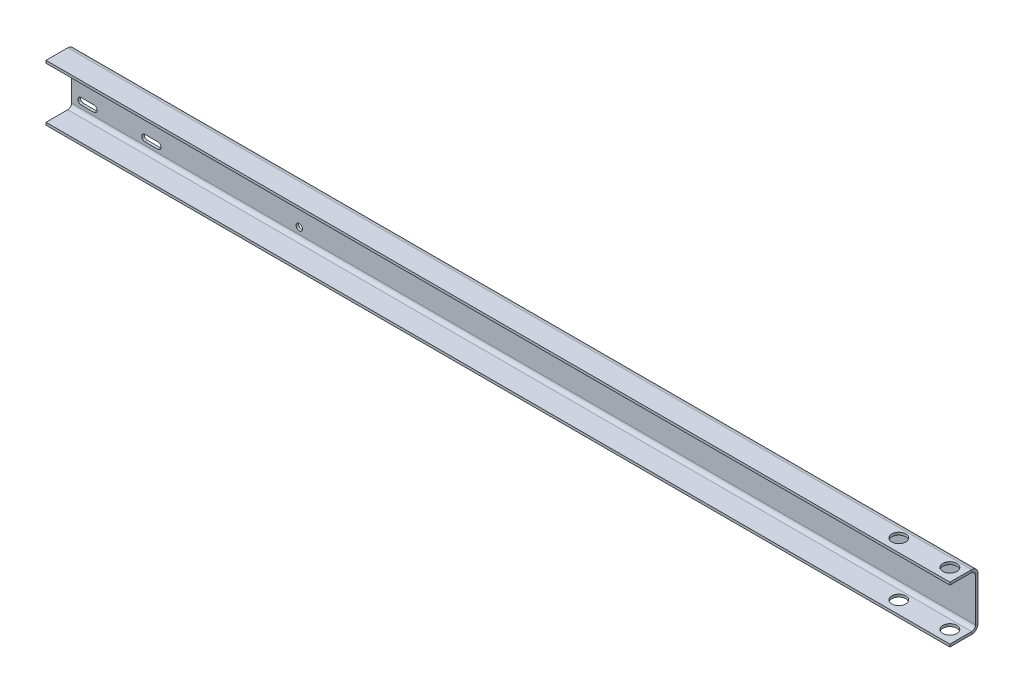
SolidWorks part; units mm, degrees
note: The reader was unsure of these and kept them because the rebuilt part matched: flange length of "Edge-Flange1", "Edge-Flange2".
material "ASTM A36 Steel"
ref_plane "Front Plane" through (0, 0, 0) normal (0, 0, 1) x (1, 0, 0)
ref_plane "Top Plane" through (0, 0, 0) normal (0, 1, 0) x (1, 0, 0)
ref_plane "Right Plane" through (0, 0, 0) normal (1, 0, 0) x (0, 0, -1)
sketch "Sketch1" plane through (0, 0, 0) normal (0, 0, 1) x (1, 0, 0)
  line L1 (549.481, 88) -> (-865.519, 88)
  line L2 (549.481, 88) -> (549.481, 0)
  line L3 (549.481, 0) -> (-865.519, 0)
  line L4 (-865.519, 88) -> (-865.519, 0)
  dimension "D1" = 88
  dimension "D2" = 1415
base flange "Base-Flange1" sketch "Sketch1" thickness 4 reverse thickness direction no parameters "D1"=2.5
edge flange "Edge-Flange1" sketch "Sketch8" flange angle 90 flange length 44 flange position material inside bend radius 6 thickness 4 relief rectangular parameters "D6"=10
sketch "Sketch8" plane through (0, 88, 0) normal (0, -1, 0) x (1, 0, 0)
  line L1 (549.481, 0) -> (-865.519, 0) construction
  line L2 (-865.519, 0) -> (-865.519, 40)
  line L3 (-865.519, 40) -> (549.481, 40)
  line L4 (549.481, 40) -> (549.481, 0)
  line L5 (549.481, 0) -> (-865.519, 0)
bend "EdgeBend1" bend radius 6 bend angle 90 parameters "D5"=1
edge flange "Edge-Flange2" sketch "Sketch11" flange angle 90 flange length 44 flange position material inside bend radius 6 thickness 4 relief rectangular parameters "D6"=10
sketch "Sketch11" plane through (0, 0, 0) normal (0, 1, 0) x (-1, 0, 0)
  line L1 (865.519, 0) -> (-549.481, 0) construction
  line L2 (-549.481, 0) -> (-549.481, 40)
  line L3 (-549.481, 40) -> (865.519, 40)
  line L4 (865.519, 40) -> (865.519, 0)
  line L5 (865.519, 0) -> (-549.481, 0)
bend "EdgeBend2" bend radius 6 bend angle 90 parameters "D5"=2
sketch "Sketch12" plane through (0, 0, 0) normal (0, -1, 0) x (1, 0, 0)
  line L0 (549.481, 40) -> (549.481, 6) construction
  circle A0 centre (529.481, 20) radius 11
  circle A1 centre (449.481, 20) radius 11
  dimension "D3" = 22
  dimension "D4" = 22
  dimension "D1" = 20
  dimension "D2" = 80
extrude "Cut-Extrude1" cut sketch "Sketch12" against normal through all both and the other way through all normal cut yes
sketch "Sketch13" plane through (0, 0, -4) normal (0, 0, -1) x (-1, 0, 0)
  line L0 (850.519, 20) -> (830.519, 20) construction
  line L1 (850.519, 15) -> (830.519, 15)
  line L2 (850.519, 25) -> (830.519, 25)
  line L3 (865.519, 0) -> (-549.481, 0) construction
  line L4 (750.519, 20) -> (730.519, 20) construction
  line L5 (750.519, 15) -> (730.519, 15)
  line L6 (750.519, 25) -> (730.519, 25)
  line L9 (865.519, 78) -> (865.519, 10) construction
  arc A0 (850.519, 15) -> (850.519, 25) centre (850.519, 20) ccw
  arc A1 (830.519, 25) -> (830.519, 15) centre (830.519, 20) ccw
  arc A4 (750.519, 15) -> (750.519, 25) centre (750.519, 20) ccw
  arc A5 (730.519, 25) -> (730.519, 15) centre (730.519, 20) ccw
  point P2 (835.519, 20)
  point P3 (840.519, 20)
  point P7 (740.519, 20)
  dimension "D5" = 20
  dimension "D6" = 100
  dimension "D7" = 15
  dimension "D8" = 0
  dimension "D1" = 20
  dimension "D2" = 10
  dimension "D3" = 20
  dimension "D4" = 10
extrude "Cut-Extrude2" cut sketch "Sketch13" against normal through all normal cut yes
sketch "Sketch16" plane through (0, 0, -4) normal (0, 0, -1) x (-1, 0, 0)
  line L0 (865.519, 20) -> (509.019, 20) construction
  line L1 (865.519, 78) -> (865.519, 10) construction
  circle A0 centre (509.019, 20) radius 5
extrude "Cut-Extrude4" cut sketch "Sketch16" against normal blind 10 normal cut yes
sketch "Bend-Lines1" [suppressed] plane through (0, 0, 0) normal (0, 1, 0) x (1, 0, 0)
sketch "Bounding-Box1" [suppressed] plane through (0, 0, 0) normal (0, 1, 0) x (1, 0, 0)
sheet metal parameters "Sheet-Metal1" thickness 4 parameters "D1"=2.5
flat pattern "Flat-Pattern1" [suppressed]
sketch "Bend-Lines2" plane through (0, 0, 0) normal (0, 1, 0) x (1, 0, 0)
sketch3d "Bounding-Box2" [suppressed]
  line L0 (865.519, 0, 0) -> (-299.481, 0, 0) construction
  line L1 (865.519, 88, 0) -> (-299.481, 88, 0) construction
  line L2 (865.519, 0, 0) -> (865.519, 88, 0) construction
  line L3 (-299.481, 0, 0) -> (-299.481, 88, 0) construction
sheet metal parameters "Sheet-Metal2" thickness 4 parameters "D1"=2.5
flat pattern "Flat-Pattern1"
sketch "Bend-Lines2" plane through (0, 0, 0) normal (0, 0, 1) x (1, 0, 0)
  line L0 (299.481, 84.2832) -> (-865.519, 84.2832) construction
  line L1 (299.481, 84.2832) -> (-865.519, 84.2832) construction
sketch3d "Bounding-Box2" [suppressed]
  line L0 (-865.519, 0, 0) -> (299.481, 0, 0) construction
  line L1 (-865.519, 124.5664, 0) -> (299.481, 124.5664, 0) construction
  line L2 (-865.519, 0, 0) -> (-865.519, 124.5664, 0) construction
  line L3 (299.481, 0, 0) -> (299.481, 124.5664, 0) construction
bend of the flat pattern "Flatten-<EdgeBend1>1"
sheet metal parameters "Sheet-Metal3" thickness 4 parameters "D1"=2.5
flat pattern "Flat-Pattern1"
sketch "Bend-Lines2" plane through (0, 0, 0) normal (0, 0, 1) x (1, 0, 0)
  line L0 (299.481, 84.2832) -> (-865.519, 84.2832) construction
  line L1 (299.481, 84.2832) -> (-865.519, 84.2832) construction
  line L2 (-865.519, 3.7168) -> (299.481, 3.7168) construction
  line L3 (-865.519, 3.7168) -> (299.481, 3.7168) construction
sketch3d "Bounding-Box2" [suppressed]
  line L0 (-865.519, -36.5664, 0) -> (299.481, -36.5664, 0) construction
  line L1 (-865.519, 124.5664, 0) -> (299.481, 124.5664, 0) construction
  line L2 (-865.519, -36.5664, 0) -> (-865.519, 124.5664, 0) construction
  line L3 (299.481, -36.5664, 0) -> (299.481, 124.5664, 0) construction
bend of the flat pattern "Flatten-<EdgeBend1>1"
bend of the flat pattern "Flatten-<EdgeBend2>1"
sheet metal parameters "Sheet-Metal4" thickness 4 parameters "D1"=2.5
flat pattern "Flat-Pattern1"
sketch "Bend-Lines2" plane through (0, 0, 0) normal (0, 0, 1) x (1, 0, 0)
  line L0 (299.481, 84.2832) -> (-865.519, 84.2832) construction
  line L1 (299.481, 84.2832) -> (-865.519, 84.2832) construction
  line L2 (-865.519, 3.7168) -> (299.481, 3.7168) construction
  line L3 (-865.519, 3.7168) -> (299.481, 3.7168) construction
sketch3d "Bounding-Box2" [suppressed]
  line L0 (-865.519, -36.5664, 0) -> (299.481, -36.5664, 0) construction
  line L1 (-865.519, 124.5664, 0) -> (299.481, 124.5664, 0) construction
  line L2 (-865.519, -36.5664, 0) -> (-865.519, 124.5664, 0) construction
  line L3 (299.481, -36.5664, 0) -> (299.481, 124.5664, 0) construction
bend of the flat pattern "Flatten-<EdgeBend1>1"
bend of the flat pattern "Flatten-<EdgeBend2>1"
sheet metal parameters "Sheet-Metal5" thickness 4 parameters "D1"=2.5
flat pattern "Flat-Pattern1" [suppressed]
sketch "Bend-Lines2" plane through (0, 0, 0) normal (0, 0, 1) x (1, 0, 0)
  line L0 (299.481, 84.2832) -> (-865.519, 84.2832) construction
  line L1 (299.481, 84.2832) -> (-865.519, 84.2832) construction
  line L2 (-865.519, 3.7168) -> (299.481, 3.7168) construction
  line L3 (-865.519, 3.7168) -> (299.481, 3.7168) construction
sketch3d "Bounding-Box2" [suppressed]
  line L0 (-865.519, -36.5664, 0) -> (299.481, -36.5664, 0) construction
  line L1 (-865.519, 124.5664, 0) -> (299.481, 124.5664, 0) construction
  line L2 (-865.519, -36.5664, 0) -> (-865.519, 124.5664, 0) construction
  line L3 (299.481, -36.5664, 0) -> (299.481, 124.5664, 0) construction
bend of the flat pattern "Flatten-<EdgeBend1>1"
bend of the flat pattern "Flatten-<EdgeBend2>1"
sketch "Sketch14-1" [suppressed] plane through (0, 3.4336, -4) normal (0, 0, -1) x (1, 0, 0)
  line L0 (-865.519, 23) -> (-519.019, 23) construction
  circle A0 centre (-519.019, 23) radius 5
sheet metal parameters "Sheet-Metal7" thickness 4 parameters "D1"=2.5
flat pattern "Flat-Pattern1"
sketch "Bend-Lines2" plane through (0, 0, 0) normal (0, 0, 1) x (1, 0, 0)
  line L0 (549.481, 84.2832) -> (-865.519, 84.2832) construction
  line L1 (549.481, 84.2832) -> (-865.519, 84.2832) construction
  line L2 (-865.519, 3.7168) -> (549.481, 3.7168) construction
  line L3 (-865.519, 3.7168) -> (549.481, 3.7168) construction
sketch3d "Bounding-Box2" [suppressed]
  line L0 (-865.519, -36.5664, 0) -> (549.481, -36.5664, 0) construction
  line L1 (-865.519, 124.5664, 0) -> (549.481, 124.5664, 0) construction
  line L2 (-865.519, -36.5664, 0) -> (-865.519, 124.5664, 0) construction
  line L3 (549.481, -36.5664, 0) -> (549.481, 124.5664, 0) construction
bend of the flat pattern "Flatten-<EdgeBend1>1"
bend of the flat pattern "Flatten-<EdgeBend2>1"
